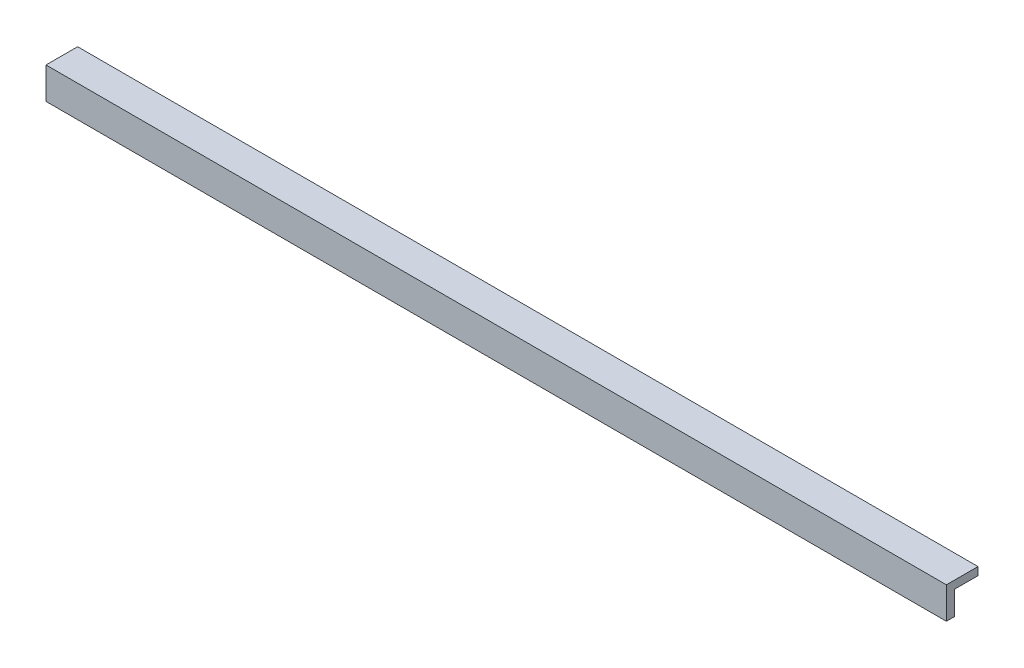
SolidWorks part; units mm, degrees
material "6061 Alloy"
ref_plane "Front Plane" through (0, 0, 0) normal (0, 0, 1) x (1, 0, 0)
ref_plane "Top Plane" through (0, 0, 0) normal (0, 1, 0) x (1, 0, 0)
ref_plane "Right Plane" through (0, 0, 0) normal (1, 0, 0) x (0, 0, -1)
sketch "Sketch1" plane through (0, 0, 0) normal (1, 0, 0) x (0, 0, -1)
  line L0 (0, 0) -> (0, 6.35)
  line L1 (0, 6.35) -> (6.35, 6.35)
  line L2 (6.35, 6.35) -> (6.35, 4.7625)
  line L3 (6.35, 4.7625) -> (1.5875, 4.7625)
  line L4 (1.5875, 4.7625) -> (1.5875, 0)
  line L5 (1.5875, 0) -> (0, 0)
  dimension "D1" = 6.35
  dimension "D2" = 6.35
  dimension "D3" = 1.5875
  dimension "D4" = 1.5875
extrude "Boss-Extrude1" add sketch "Sketch1" along normal blind 180.848
